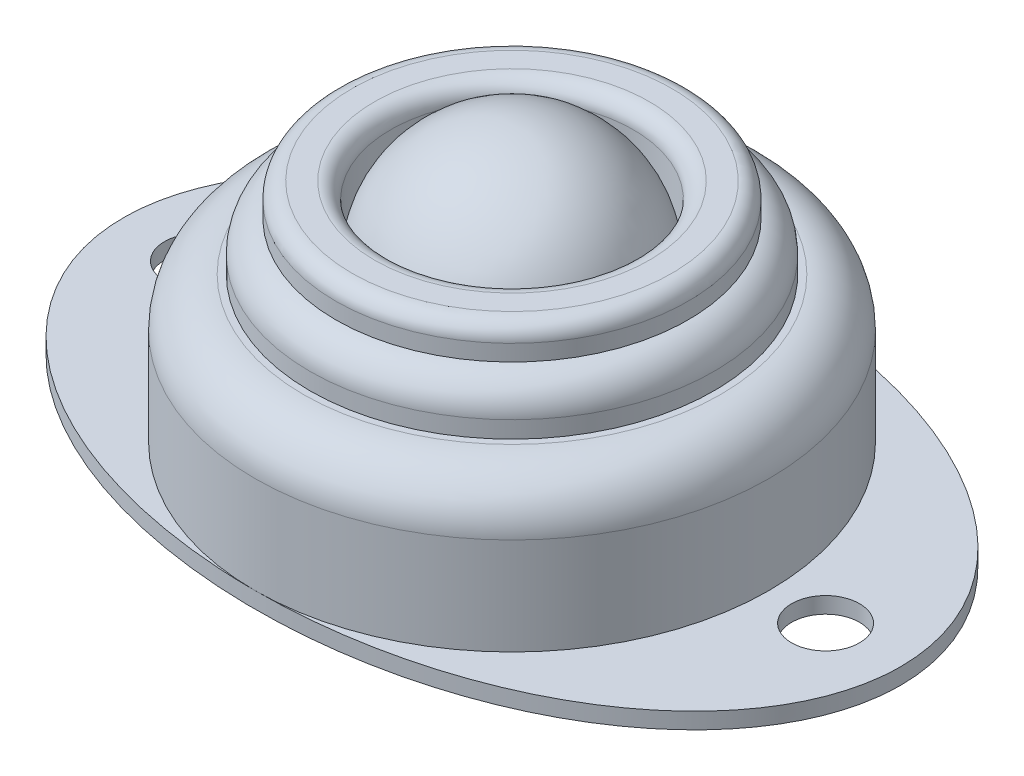
SolidWorks part; units mm, degrees
ref_plane "前视基准面" through (0, 0, 0) normal (0, 0, 1) x (1, 0, 0)
ref_plane "上视基准面" through (0, 0, 0) normal (0, 1, 0) x (1, 0, 0)
ref_plane "右视基准面" through (0, 0, 0) normal (1, 0, 0) x (0, 0, -1)
sketch "草图1" plane through (0, 0, 0) normal (0, 1, 0) x (1, 0, 0)
  line L0 (-24.05, 0) -> (24.05, 0) construction
  line L1 (0, 15.9) -> (0, -15.9) construction
  circle A0 centre (0, 0) radius 15.9
  circle A1 centre (-19.4, 0) radius 2.1
  circle A2 centre (19.4, 0) radius 2.1
  ellipse E0 centre (0, 0) end of major axis (24.05, 0) minor radius 15.9
  point P16 (0, 0)
  dimension "D1" = 31.8
  dimension "D3" = 38.8
  dimension "D4" = 4.2
  dimension "D2" = 24.05
extrude "凸台-拉伸1" add sketch "草图1" along normal blind 1 contours A0 E0 A1 | A0 | A0 E0 A2 region at (0, 0, 0) region at (16.7768, 0, 0) region at (-16.7768, 0, 0)
extrude "凸台-拉伸2" add sketch "草图1<3>" along normal blind 15 contours A0
sketch "草图1<3>" plane through (0, 0, 0) normal (0, 1, 0) x (1, 0, 0) same geometry as "草图1"
sketch "草图2" plane through (0, 15, 0) normal (0, 1, 0) x (1, 0, 0)
  circle A0 centre (0, 0) radius 7.5
  dimension "D1" = 15
extrude "切除-拉伸2" cut sketch "草图2" against normal blind 12 contours A0
sketch "草图5" plane through (0, 3, 0) normal (0, 1, 0) x (1, 0, 0)
  circle A0 centre (0, 0) radius 7.5
extrude "凸台-拉伸4" add sketch "草图5" along normal blind 15 separate body
fillet "圆角4" radius 7.5 2 edges at (0, 3, 7.5) (0, 18, 7.5)
sketch "草图6" plane through (0, 15, 0) normal (0, 1, 0) x (1, 0, 0)
  circle A0 centre (0, 0) radius 12.5
  circle A1 centre (0, 0) radius 15.9
  dimension "D1" = 25
extrude "切除-拉伸3" cut sketch "草图6" against normal blind 5
sketch "草图7" plane through (0, 15, 0) normal (0, 1, 0) x (1, 0, 0)
  circle A0 centre (0, 0) radius 12.5
  circle A1 centre (0, 0) radius 10.9
  circle A2 centre (0, 0) radius 15.9 construction
  dimension "D1" = 5
extrude "切除-拉伸4" cut sketch "草图7" against normal blind 2
fillet "圆角5" radius 1 2 edges at (0, 15, 10.9) (0, 15, 7.5)
fillet "圆角8" radius 3 1 edges at (0, 10, 15.9)
fillet "圆角9" radius 2 1 edges at (0, 13, 12.5)
